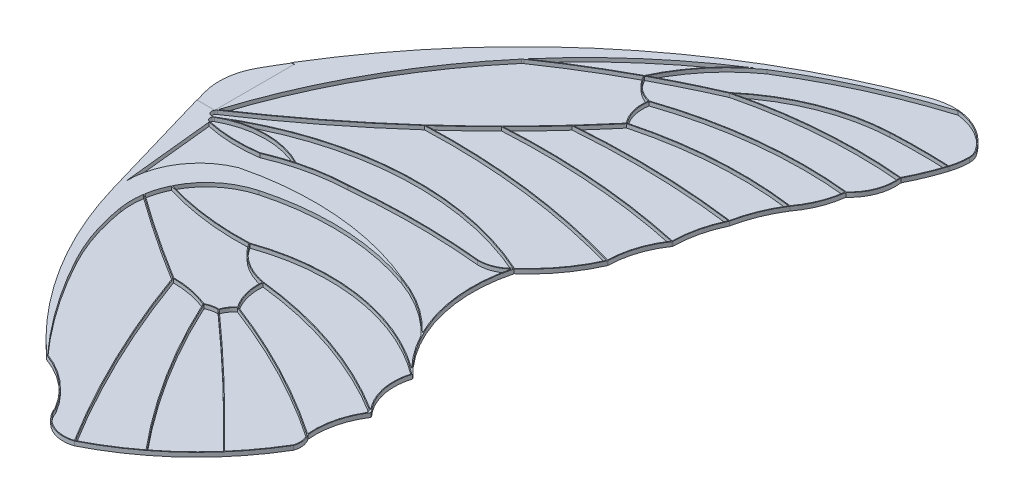
SolidWorks part; units mm, degrees
ref_plane "Plano frontal" through (0, 0, 0) normal (0, 0, 1) x (1, 0, 0)
ref_plane "Plano superior" through (0, 0, 0) normal (0, 1, 0) x (1, 0, 0)
ref_plane "Plano direito" through (0, 0, 0) normal (1, 0, 0) x (0, 0, -1)
sketch "Esboço1" plane through (0, 0, 0) normal (0, 1, 0) x (1, 0, 0)
  line L0 (245.8971, 320.852) -> (1229.6128, 320.852) construction
  line L1 (16.8906, -92.872) -> (-2.8919, -25.3314)
  line L3 (11.8593, -37.4647) -> (16.8906, -86.1328)
  arc A0 (-2.8919, -25.3314) -> (0, 0) centre (28.6286, -16.0991) cw
  arc A1 (0, 0) -> (189.3972, 162.1056) centre (316.3195, -177.8795) cw
  arc A3 (225.6385, 150.4697) -> (227.1081, 145.6019) centre (218.3116, 145.6019) cw construction
  arc A4 (227.1081, 145.6019) -> (225.6385, 136.1666) centre (196.0862, 145.6019) cw construction
  arc A5 (225.6385, 136.1666) -> (218.3116, 118.3563) centre (112.5985, 172.257) cw construction
  arc A7 (218.3116, 118.3563) -> (210.4763, 97.5461) centre (194.6459, 115.3865) cw construction
  arc A8 (210.4763, 97.5461) -> (202.0473, 76.5423) centre (166.9708, 102.8121) cw construction
  arc A9 (202.0473, 76.5423) -> (192.9964, 53.9892) centre (259.2241, 40.5039) ccw construction
  arc A10 (192.9964, 53.9892) -> (187.293, 29.7021) centre (245.6081, 28.8209) ccw construction
  arc A11 (187.293, 29.7021) -> (179.0373, 4.0907) centre (225.0788, 3.3859) ccw construction
  arc A12 (179.0373, 4.0907) -> (158.23, -24.0759) centre (104.6802, 37.2514) cw construction
  arc A15 (158.23, -24.0759) -> (13.4854, -32.4272) centre (93.7944, -165.8093) ccw construction
  arc A16 (158.23, -24.0759) -> (177.8517, -97.0522) centre (231.9136, -43.3901) ccw construction
  arc A17 (8.5132, -29.7405) -> (121.9031, 71.3535) centre (-285.6091, 414.2929) ccw construction
  arc A18 (11.0704, -33.894) -> (11.8796, -37.06) centre (11.8906, -35.3708) ccw
  arc A19 (69.7615, 17.5747) -> (179.0373, 4.0907) centre (83.0084, -324.6055) cw construction
  arc A20 (187.293, 29.7021) -> (90.5728, 37.2507) centre (111.635, -316.2908) ccw construction
  arc A21 (192.9964, 53.9892) -> (108.6142, 56.1566) centre (140.5341, -344.8129) ccw construction
  arc A22 (202.0473, 76.5423) -> (121.9031, 71.3535) centre (174.9731, -126.811) ccw construction
  arc A23 (121.9031, 71.3535) -> (117.6553, 87.2147) centre (137.0585, 83.9116) cw construction
  arc A24 (117.6553, 87.2147) -> (210.4763, 97.5461) centre (187.5432, -118.5488) cw construction
  arc A25 (202.7141, 163.713) -> (134.2312, 132.489) centre (289.7224, -117.8339) ccw
  arc A26 (65.7605, 73.6867) -> (134.9405, 112.1301) centre (303.5466, -272.7489) cw construction
  arc A27 (117.6553, 87.2147) -> (104.9295, 97.5363) centre (122.326, 105.9791) cw construction
  arc A28 (105.0708, 97.8389) -> (131.9285, 131.0439) centre (185.93, 59.9007) cw construction
  arc A29 (134.9405, 112.1301) -> (195.1764, 136.1273) centre (199.9365, 36.5807) cw construction
  arc A30 (134.9405, 112.1301) -> (218.3116, 118.3563) centre (194.9004, -129.4588) cw construction
  arc A31 (195.1764, 136.1273) -> (225.6385, 136.1666) centre (210.8302, -191.2388) cw construction
  arc A32 (164.2786, -78.4304) -> (163.8648, -78.0625) centre (76.6095, -176.6501) ccw construction
  arc A33 (40.2619, -50.4484) -> (16.8906, -86.1328) centre (54.6574, -85.3723) ccw
  arc A34 (11.8377, -37.2556) -> (39.3063, -38.1782) centre (28.1448, 38.8778) ccw construction
  arc A35 (39.3063, -38.1782) -> (77.0189, -29.7405) centre (80.4783, -133.7) cw construction
  arc A36 (77.0189, -29.7405) -> (145.0691, -29.7551) centre (110.9705, -372.2463) cw construction
  arc A37 (145.0691, -29.7551) -> (158.23, -24.0759) centre (145.2218, -12.02) ccw construction
  arc A38 (53.1607, -33.3342) -> (13.4854, -32.4272) centre (32.4211, -72.3358) ccw construction
  arc A39 (38.8997, -20.1148) -> (13.4854, -32.4272) centre (28.6163, -31.2738) cw construction
  arc A40 (16.8906, -92.872) -> (74.9246, -185.6146) centre (210.7556, -36.0892) ccw
  arc A41 (74.9929, -185.4267) -> (66.3816, -175.3804) centre (154.2645, -108.7641) cw construction
  arc A42 (39.4144, -134.6037) -> (75.0612, -185.2387) centre (266.3145, -12.7322) ccw
  arc A43 (74.9929, -185.4267) -> (101.4999, -207.5656) centre (57.6789, -233.0946) cw construction
  arc A44 (101.4999, -207.5656) -> (121.3412, -217.2503) centre (116.2629, -202.4873) ccw construction
  arc A45 (121.3412, -217.2503) -> (180.55, -161.9238) centre (55.9487, -87.924) ccw construction
  arc A46 (180.55, -161.9238) -> (179.3854, -153.5104) centre (171.7806, -158.8504) ccw construction
  arc A47 (179.3754, -98.5448) -> (185.959, -126.7273) centre (206.845, -106.9879) ccw construction
  arc A48 (185.959, -126.7273) -> (179.3854, -153.5104) centre (220.4313, -149.3865) ccw construction
  arc A49 (103.607, -114.0548) -> (179.3854, -153.5104) centre (-25.2756, -454.0845) cw construction
  arc A50 (55.95, -55.4784) -> (133.7088, -58.3585) centre (90.2455, -180.677) cw
  arc A51 (55.95, -55.4784) -> (31.1326, -75.9422) centre (66.32, -93.3351) ccw
  arc A52 (27.5649, -99.5565) -> (39.4144, -134.6037) centre (137.5319, -81.9033) ccw
  arc A53 (27.565, -87.1132) -> (73.2426, -117.5725) centre (461.4317, 514.0462) ccw construction
  arc A54 (73.2426, -117.5725) -> (92.998, -121.4212) centre (73.3114, -169.8452) cw construction
  arc A55 (92.998, -121.4212) -> (99.4217, -119.9985) centre (98.6915, -131.9152) cw construction
  arc A56 (99.4217, -119.9985) -> (103.607, -114.0548) centre (110.0937, -123.0679) cw construction
  arc A57 (103.607, -114.0548) -> (98.6915, -96.0121) centre (125.3192, -98.4486) cw construction
  arc A58 (98.6915, -96.0121) -> (77.4929, -81.9059) centre (103.8031, -65.3487) cw construction
  arc A59 (77.4929, -81.9059) -> (178.9645, -98.1504) centre (113.3271, -183.1111) cw construction
  arc A60 (77.4929, -81.9059) -> (31.0432, -76.1242) centre (71.4634, 59.1311) cw construction
  arc A61 (98.6915, -96.0121) -> (185.959, -126.7273) centre (76.8879, -297.2892) cw construction
  arc A62 (99.4217, -119.9985) -> (165.2455, -183.0853) centre (-749.6332, -1071.7733) cw construction
  arc A63 (92.998, -121.4212) -> (144.3602, -202.7494) centre (428.3218, 33.4673) ccw construction
  arc A64 (73.2426, -117.5725) -> (121.3412, -217.2503) centre (570.6991, 61.0271) ccw construction
  arc A65 (8.6464, -29.8922) -> (10.8842, -33.7922) centre (9.8905, -31.7703) ccw
  arc A66 (65.8737, 73.5218) -> (65.1633, 72.9862) centre (71.5226, 65.2919) ccw
  arc A67 (104.7763, 97.681) -> (130.1059, 129.8789) centre (185.93, 59.9007) cw
  arc A68 (104.7481, 97.6206) -> (150.4255, 142.0756) centre (185.93, 59.9007) cw construction
  arc A69 (104.9295, 97.5363) -> (150.5048, 141.892) centre (185.93, 59.9007) cw construction
  arc A70 (130.1059, 129.8789) -> (66.2643, 74.2743) centre (289.7224, -117.8339) ccw
  arc A71 (65.1633, 72.9862) -> (8.6083, -29.4376) centre (289.7224, -117.8339) ccw
  arc A72 (135.7135, 112.5265) -> (195.186, 135.9275) centre (199.9365, 36.5807) cw
  arc A73 (134.8328, 112.3013) -> (195.1668, 136.3271) centre (199.9365, 36.5807) cw
  arc A74 (65.8737, 73.5218) -> (104.8415, 97.2621) centre (303.5466, -272.7489) cw
  arc A75 (66.2643, 74.2743) -> (104.7763, 97.681) centre (303.5466, -272.7489) cw
  arc A76 (105.3664, 97.9971) -> (134.2312, 132.489) centre (185.93, 59.9007) cw
  arc A77 (105.3664, 97.9971) -> (134.8328, 112.3013) centre (303.5466, -272.7489) cw
  arc A78 (65.6474, 73.8516) -> (134.8603, 112.3133) centre (303.5466, -272.7489) cw construction
  arc A79 (203.4113, 163.9275) -> (225.6385, 150.4697) centre (200.23, 133.5888) cw construction
  arc A80 (203.3904, 163.7286) -> (225.4719, 150.359) centre (200.23, 133.5888) cw
  arc A81 (203.4321, 164.1264) -> (225.805, 150.5804) centre (200.23, 133.5888) cw
  arc A82 (189.3972, 162.1056) -> (203.4321, 164.1264) centre (201.0573, 130.8716) cw
  arc A83 (203.3904, 163.7286) -> (202.7141, 163.713) centre (203.1131, 161.0838) ccw
  arc A84 (225.4719, 150.359) -> (226.9081, 145.6019) centre (218.3116, 145.6019) cw
  arc A85 (226.9081, 145.6019) -> (225.4941, 136.3733) centre (196.0862, 145.6019) cw
  arc A86 (225.805, 150.5804) -> (227.3081, 145.6019) centre (218.3116, 145.6019) cw
  arc A87 (227.3081, 145.6019) -> (225.829, 136.1058) centre (196.0862, 145.6019) cw
  arc A88 (195.186, 135.9275) -> (225.3682, 135.9786) centre (210.8302, -191.2388) cw
  arc A89 (195.1668, 136.3271) -> (225.4941, 136.3733) centre (210.8302, -191.2388) cw
  arc A90 (195.1668, 136.3271) -> (225.6475, 136.3664) centre (210.8302, -191.2388) cw construction
  arc A91 (226.9081, 145.6019) -> (225.4479, 136.2275) centre (196.0862, 145.6019) cw construction
  arc A92 (225.3682, 135.9786) -> (218.195, 118.5681) centre (112.5985, 172.257) cw
  arc A93 (135.0052, 111.9401) -> (218.1326, 118.1722) centre (194.9004, -129.4588) cw
  arc A94 (218.1326, 118.1722) -> (210.4094, 97.7543) centre (194.6459, 115.3865) cw
  arc A95 (225.829, 136.1058) -> (218.5176, 118.3201) centre (112.5985, 172.257) cw
  arc A96 (135.7135, 112.5265) -> (218.195, 118.5681) centre (194.9004, -129.4588) cw
  arc A97 (218.5176, 118.3201) -> (210.6657, 97.4469) centre (194.6459, 115.3865) cw
  arc A98 (225.4479, 136.2275) -> (218.1334, 118.4471) centre (112.5985, 172.257) cw construction
  arc A99 (134.8923, 112.3242) -> (218.3304, 118.5554) centre (194.9004, -129.4588) cw construction
  arc A100 (195.186, 135.9275) -> (225.6294, 135.9669) centre (210.8302, -191.2388) cw construction
  arc A101 (134.8101, 112.2817) -> (195.1668, 136.3271) centre (199.9365, 36.5807) cw construction
  arc A102 (135.0709, 111.9785) -> (195.186, 135.9275) centre (199.9365, 36.5807) cw construction
  arc A103 (134.9887, 111.936) -> (218.2928, 118.1572) centre (194.9004, -129.4588) cw construction
  arc A104 (65.8737, 73.5218) -> (135.0208, 111.9469) centre (303.5466, -272.7489) cw construction
  arc A105 (218.51, 118.3812) -> (210.6091, 97.3965) centre (194.6459, 115.3865) cw construction
  arc A106 (225.829, 136.1058) -> (218.4898, 118.2654) centre (112.5985, 172.257) cw construction
  arc A107 (218.1131, 118.3314) -> (210.3436, 97.6957) centre (194.6459, 115.3865) cw construction
  arc A108 (117.6468, 87.423) -> (105.1942, 97.4512) centre (122.326, 105.9791) cw
  arc A109 (121.9757, 71.58) -> (117.8329, 87.0637) centre (137.0585, 83.9116) cw
  arc A110 (117.8329, 87.0637) -> (210.2529, 97.3685) centre (187.5432, -118.5488) cw
  arc A111 (210.2529, 97.3685) -> (201.9573, 76.7561) centre (166.9708, 102.8121) cw
  arc A112 (117.428, 87.066) -> (104.8415, 97.2621) centre (122.326, 105.9791) cw
  arc A113 (121.643, 71.3551) -> (117.428, 87.066) centre (137.0585, 83.9116) cw
  arc A114 (117.6468, 87.423) -> (210.4094, 97.7543) centre (187.5432, -118.5488) cw
  arc A115 (210.6657, 97.4469) -> (202.2122, 76.4289) centre (166.9708, 102.8121) cw
  arc A116 (105.1942, 97.4512) -> (135.0052, 111.9401) centre (303.5466, -272.7489) cw
  arc A117 (117.607, 87.0206) -> (104.7496, 97.449) centre (122.326, 105.9791) cw construction
  arc A118 (117.7036, 87.4087) -> (105.1094, 97.6236) centre (122.326, 105.9791) cw construction
  arc A119 (121.7491, 71.2259) -> (117.4582, 87.2482) centre (137.0585, 83.9116) cw construction
  arc A120 (117.7197, 87.0253) -> (210.2529, 97.3685) centre (187.5432, -118.5488) cw construction
  arc A121 (122.0571, 71.4811) -> (117.8525, 87.1811) centre (137.0585, 83.9116) cw construction
  arc A122 (117.591, 87.404) -> (210.6988, 97.7235) centre (187.5432, -118.5488) cw construction
  arc A123 (201.7125, 76.3849) -> (192.8379, 54.2118) centre (259.2241, 40.5039) ccw
  arc A124 (210.6988, 97.7235) -> (202.2073, 76.4225) centre (166.9708, 102.8121) cw construction
  arc A125 (202.2122, 76.4289) -> (193.1924, 53.9493) centre (259.2241, 40.5039) ccw
  arc A126 (201.9573, 76.7561) -> (121.9757, 71.58) centre (174.9731, -126.811) ccw
  arc A127 (193.1924, 53.9493) -> (193.1768, 53.9029) centre (192.9964, 53.9892) cw
  arc A128 (8.6464, -29.8922) -> (69.8412, 17.3776) centre (-285.6091, 414.2929) ccw
  arc A129 (8.6083, -29.4376) -> (121.643, 71.3551) centre (-285.6091, 414.2929) ccw
  arc A130 (192.8379, 54.2118) -> (109.1013, 56.3957) centre (140.5341, -344.8129) ccw
  arc A131 (202.2165, 76.4357) -> (193.1924, 53.9493) centre (259.2241, 40.5039) ccw construction
  arc A132 (8.4027, -29.5738) -> (121.7501, 71.4823) centre (-285.6091, 414.2929) ccw construction
  arc A133 (202.0737, 76.7406) -> (121.8513, 71.5467) centre (174.9731, -126.811) ccw construction
  arc A134 (187.0972, 29.9495) -> (91.0867, 37.4813) centre (111.635, -316.2908) ccw
  arc A135 (8.6236, -29.9073) -> (122.0561, 71.2247) centre (-285.6091, 414.2929) ccw construction
  arc A136 (193.0225, 54.1875) -> (108.5983, 56.356) centre (140.5341, -344.8129) ccw construction
  arc A137 (69.8412, 17.3776) -> (178.761, 3.963) centre (83.0084, -324.6055) cw
  arc A138 (109.1013, 56.3957) -> (122.0156, 71.1766) centre (-285.6091, 414.2929) ccw
  arc A139 (201.8781, 76.649) -> (192.8004, 54.0291) centre (259.2241, 40.5039) ccw construction
  arc A140 (210.2529, 97.3685) -> (201.8872, 76.6622) centre (166.9708, 102.8121) cw construction
  arc A141 (201.7125, 76.3849) -> (122.0156, 71.1766) centre (174.9731, -126.811) ccw
  arc A142 (193.1768, 53.9029) -> (187.4952, 29.8402) centre (245.6081, 28.8209) ccw
  arc A143 (187.3768, 29.4721) -> (187.4952, 29.8402) centre (186.8279, 29.8519) ccw
  arc A144 (187.0972, 29.9495) -> (90.5609, 37.4504) centre (111.635, -316.2908) ccw construction
  arc A145 (91.0867, 37.4813) -> (108.709, 55.9635) centre (-285.6091, 414.2929) ccw
  arc A146 (187.4898, 29.4542) -> (90.5847, 37.0511) centre (111.635, -316.2908) ccw construction
  arc A147 (192.6977, 53.8267) -> (187.0972, 29.9495) centre (245.6081, 28.8209) ccw
  arc A148 (192.816, 54.0755) -> (187.0972, 29.9495) centre (245.6081, 28.8209) ccw construction
  arc A149 (192.6977, 53.8267) -> (108.709, 55.9635) centre (140.5341, -344.8129) ccw
  arc A150 (187.3768, 29.4721) -> (179.2373, 4.0876) centre (225.0788, 3.3859) ccw
  arc A151 (70.3073, 17.7955) -> (178.8421, 4.356) centre (83.0084, -324.6055) cw
  arc A152 (186.9587, 29.5703) -> (178.8421, 4.356) centre (225.0788, 3.3859) ccw
  arc A153 (69.7538, 17.7745) -> (178.8421, 4.356) centre (83.0084, -324.6055) cw construction
  arc A154 (70.3073, 17.7955) -> (90.6603, 37.0556) centre (-285.6091, 414.2929) ccw
  arc A155 (69.7692, 17.3748) -> (179.2341, 3.8248) centre (83.0084, -324.6055) cw construction
  arc A156 (187.1288, 29.8164) -> (178.8421, 4.356) centre (225.0788, 3.3859) ccw construction
  arc A157 (186.9587, 29.5703) -> (90.6603, 37.0556) centre (111.635, -316.2908) ccw
  arc A158 (187.4571, 29.5878) -> (179.2341, 3.8248) centre (225.0788, 3.3859) ccw construction
  arc A159 (193.1768, 53.9029) -> (187.4898, 29.4542) centre (245.6081, 28.8209) ccw construction
  arc A160 (178.8547, 4.1721) -> (178.8436, 4.1472) centre (104.6802, 37.2514) cw
  arc A161 (158.1953, -23.8405) -> (10.8842, -33.7922) centre (93.7944, -165.8093) ccw
  arc A162 (179.22, 4.0092) -> (158.4079, -24.186) centre (104.6802, 37.2514) cw
  arc A163 (179.22, 4.0092) -> (158.2644, -24.3113) centre (104.6802, 37.2514) cw construction
  arc A165 (158.1953, -23.8405) -> (13.3822, -32.2559) centre (93.7944, -165.8093) ccw construction
  arc A167 (53.1846, -33.1205) -> (16.3441, -30.9777) centre (32.4211, -72.3358) ccw
  arc A168 (11.8593, -37.4647) -> (39.3612, -38.3724) centre (28.1448, 38.8778) ccw
  arc A169 (39.3612, -38.3724) -> (77.0321, -29.9402) centre (80.4783, -133.7) cw
  arc A170 (77.0321, -29.9402) -> (145.0582, -29.9551) centre (110.9705, -372.2463) cw
  arc A171 (145.0582, -29.9551) -> (157.8482, -24.7583) centre (145.2218, -12.02) ccw
  arc A172 (145.0582, -29.9551) -> (158.3767, -24.2119) centre (145.2218, -12.02) ccw construction
  arc A173 (11.8796, -37.06) -> (39.2515, -37.9841) centre (28.1448, 38.8778) ccw
  arc A174 (39.2515, -37.9841) -> (52.6186, -33.2758) centre (80.4783, -133.7) cw
  arc A175 (77.0057, -29.5409) -> (145.0798, -29.5552) centre (110.9705, -372.2463) cw
  arc A176 (145.0798, -29.5552) -> (157.8927, -24.1424) centre (145.2218, -12.02) ccw
  arc A177 (53.2546, -33.1576) -> (13.3997, -32.2465) centre (32.4211, -72.3358) ccw construction
  arc A178 (11.7958, -37.4511) -> (39.3612, -38.3724) centre (28.1448, 38.8778) ccw construction
  arc A179 (158.2644, -24.3113) -> (13.5886, -32.5986) centre (93.7944, -165.8093) ccw construction
  arc A180 (145.0798, -29.5552) -> (158.0833, -23.94) centre (145.2218, -12.02) ccw construction
  arc A182 (52.6186, -33.2758) -> (11.0704, -33.894) centre (32.4211, -72.3358) ccw
  arc A183 (53.1846, -33.1205) -> (77.0057, -29.5409) centre (80.4783, -133.7) cw
  arc A184 (39.2515, -37.9841) -> (77.0057, -29.5409) centre (80.4783, -133.7) cw construction
  arc A185 (157.8927, -24.1424) -> (16.3441, -30.9777) centre (93.7944, -165.8093) ccw
  arc A186 (178.761, 3.963) -> (158.1953, -23.8405) centre (104.6802, 37.2514) cw
  arc A187 (178.8547, 4.1721) -> (158.1953, -23.8405) centre (104.6802, 37.2514) cw construction
  arc A188 (179.22, 4.0092) -> (179.2373, 4.0876) centre (179.0373, 4.0907) ccw
  arc A189 (157.8482, -24.7583) -> (163.5415, -77.4206) centre (231.9136, -43.3901) ccw
  arc A190 (158.4079, -24.186) -> (179.5133, -98.4) centre (231.9136, -43.3901) ccw
  arc A191 (158.0365, -24.0252) -> (179.2374, -98.6896) centre (231.9136, -43.3901) ccw construction
  arc A192 (133.8427, -57.9816) -> (40.2619, -50.4484) centre (75.882, -192.9794) ccw
  arc A193 (158.4235, -24.1266) -> (179.5133, -98.4) centre (231.9136, -43.3901) ccw construction
  arc A194 (133.7758, -58.17) -> (163.8648, -78.0625) centre (108.6533, -128.872) cw construction
  arc A195 (133.7088, -58.3585) -> (163.7246, -78.2055) centre (108.6533, -128.872) cw
  arc A196 (163.7246, -78.2055) -> (164.2392, -78.7877) centre (149.3526, -91.428) cw
  arc A197 (133.8427, -57.9816) -> (163.5415, -77.4206) centre (108.6533, -128.872) cw
  arc A198 (77.3856, -82.1106) -> (30.9549, -76.3065) centre (71.4634, 59.1311) cw
  arc A199 (133.8427, -57.9816) -> (164.005, -77.9196) centre (108.6533, -128.872) cw construction
  arc A200 (164.1455, -78.5796) -> (163.7246, -78.2055) centre (76.6095, -176.6501) ccw construction
  arc A201 (164.2392, -78.7877) -> (176.8413, -96.3038) centre (231.9136, -43.3901) ccw
  arc A202 (164.4118, -78.2811) -> (164.005, -77.9196) centre (76.6095, -176.6501) ccw construction
  arc A203 (77.7964, -82.0109) -> (178.8422, -98.3087) centre (113.3271, -183.1111) cw
  arc A204 (77.4544, -81.7073) -> (31.1326, -75.9422) centre (71.4634, 59.1311) cw
  arc A205 (77.4544, -81.7073) -> (176.8413, -96.3038) centre (113.3271, -183.1111) cw
  arc A206 (77.5314, -82.1044) -> (30.986, -76.3158) centre (71.4634, 59.1311) cw construction
  arc A207 (30.9549, -76.3065) -> (27.6041, -86.8743) centre (66.32, -93.3351) ccw
  arc A208 (77.4544, -81.7073) -> (31.1005, -75.9326) centre (71.4634, 59.1311) cw construction
  arc A209 (158.23, -24.0759) -> (179.3754, -98.5448) centre (231.9136, -43.3901) ccw construction
  arc A210 (98.7187, -95.8139) -> (77.7964, -82.0109) centre (103.8031, -65.3487) cw
  arc A211 (103.7344, -113.8892) -> (98.8729, -96.233) centre (125.3192, -98.4486) cw
  arc A212 (98.713, -95.8133) -> (184.8389, -125.7798) centre (76.8879, -297.2892) cw construction
  arc A213 (179.5665, -98.6035) -> (185.9696, -126.4464) centre (206.845, -106.9879) ccw
  arc A214 (98.4761, -96.1784) -> (77.3856, -82.1106) centre (103.8031, -65.3487) cw
  arc A215 (103.3296, -114.0103) -> (98.4761, -96.1784) centre (125.3192, -98.4486) cw
  arc A216 (98.7187, -95.8139) -> (184.8389, -125.7798) centre (76.8879, -297.2892) cw
  arc A217 (179.5133, -98.4) -> (179.5665, -98.6035) centre (179.3754, -98.5448) cw
  arc A218 (98.6586, -96.2094) -> (77.3236, -82.0124) centre (103.8031, -65.3487) cw construction
  arc A219 (77.5314, -82.1044) -> (178.8422, -98.3087) centre (113.3271, -183.1111) cw construction
  arc A220 (178.8422, -98.3087) -> (179.0485, -98.9406) centre (178.4809, -98.7763) cw
  arc A221 (98.7244, -95.8148) -> (77.6621, -81.7994) centre (103.8031, -65.3487) cw construction
  arc A222 (77.4544, -81.7073) -> (179.0867, -97.9922) centre (113.3271, -183.1111) cw construction
  arc A223 (99.6493, -119.9335) -> (103.6372, -114.2802) centre (110.0937, -123.0679) cw
  arc A224 (179.0485, -98.9406) -> (184.8389, -125.7798) centre (206.845, -106.9879) ccw
  arc A225 (179.1842, -98.486) -> (184.8389, -125.7798) centre (206.845, -106.9879) ccw construction
  arc A226 (103.6372, -114.2802) -> (179.2425, -153.6551) centre (-25.2756, -454.0845) cw
  arc A227 (186.018, -127.0026) -> (179.5792, -153.4387) centre (220.4313, -149.3865) ccw
  arc A228 (99.2747, -119.7902) -> (103.3296, -114.0103) centre (110.0937, -123.0679) cw
  arc A229 (103.7344, -113.8892) -> (179.1459, -153.1057) centre (-25.2756, -454.0845) cw
  arc A230 (185.7919, -126.6175) -> (185.7905, -126.6196) centre (220.4313, -149.3865) ccw
  arc A231 (184.6648, -128.4325) -> (179.1459, -153.1057) centre (220.4313, -149.3865) ccw
  arc A232 (185.7919, -126.6175) -> (179.1459, -153.1057) centre (220.4313, -149.3865) ccw construction
  arc A233 (186.1262, -126.8372) -> (179.6297, -153.919) centre (220.4313, -149.3865) ccw construction
  arc A234 (98.6699, -96.2109) -> (187.474, -127.9445) centre (76.8879, -297.2892) cw construction
  arc A235 (186.018, -127.0026) -> (185.9696, -126.4464) centre (185.6381, -126.7554) ccw
  arc A236 (179.5665, -98.6035) -> (187.474, -127.9445) centre (206.845, -106.9879) ccw construction
  arc A237 (184.6648, -128.4325) -> (183.9983, -125.7249) centre (182.9391, -127.4215) ccw
  arc A238 (93.2588, -121.5089) -> (99.3405, -120.1941) centre (98.6915, -131.9152) cw
  arc A239 (99.3405, -120.1941) -> (164.9738, -183.0926) centre (-749.6332, -1071.7733) cw
  arc A240 (121.4315, -217.4287) -> (180.7321, -162.0089) centre (55.9487, -87.924) ccw
  arc A241 (180.7321, -162.0089) -> (179.5792, -153.4387) centre (171.7806, -158.8504) ccw
  arc A242 (92.986, -121.2005) -> (99.2747, -119.7902) centre (98.6915, -131.9152) cw
  arc A243 (99.6493, -119.9335) -> (165.2373, -182.7899) centre (-749.6332, -1071.7733) cw
  arc A244 (121.4146, -216.9889) -> (144.0736, -202.7175) centre (55.9487, -87.924) ccw
  arc A245 (180.3678, -161.8389) -> (179.2425, -153.6551) centre (171.7806, -158.8504) ccw
  arc A246 (99.2295, -119.9432) -> (103.578, -113.83) centre (110.0937, -123.0679) cw construction
  arc A247 (103.578, -113.83) -> (179.1459, -153.1057) centre (-25.2756, -454.0845) cw construction
  arc A248 (92.9026, -121.2454) -> (99.5034, -119.8034) centre (98.6915, -131.9152) cw construction
  arc A249 (99.6139, -120.0538) -> (103.6372, -114.2802) centre (110.0937, -123.0679) cw construction
  arc A250 (99.5034, -119.8034) -> (165.389, -182.9459) centre (-749.6332, -1071.7733) cw construction
  arc A251 (103.7694, -113.9381) -> (98.8906, -96.0303) centre (125.3192, -98.4486) cw construction
  arc A252 (103.4446, -114.1716) -> (98.4923, -95.9939) centre (125.3192, -98.4486) cw construction
  arc A253 (180.3678, -161.8389) -> (179.2217, -153.6253) centre (171.7806, -158.8504) ccw construction
  arc A254 (98.8729, -96.233) -> (183.9983, -125.7249) centre (76.8879, -297.2892) cw
  arc A255 (103.6372, -114.2802) -> (179.6297, -153.919) centre (-25.2756, -454.0845) cw construction
  arc A256 (180.7321, -162.0089) -> (179.549, -153.3955) centre (171.7806, -158.8504) ccw construction
  arc A257 (165.3772, -182.9338) -> (165.389, -182.9459) centre (-749.6332, -1071.7733) cw
  arc A258 (165.2373, -182.7899) -> (180.3678, -161.8389) centre (55.9487, -87.924) ccw
  arc A259 (121.251, -217.0718) -> (180.3678, -161.8389) centre (55.9487, -87.924) ccw construction
  arc A260 (99.3405, -120.1941) -> (165.102, -183.2246) centre (-749.6332, -1071.7733) cw construction
  arc A261 (121.4315, -217.4287) -> (121.4146, -217.4365) centre (121.315, -217.1984) cw
  arc A262 (92.8496, -121.5768) -> (144.0736, -202.7175) centre (428.3218, 33.4673) ccw
  arc A263 (73.2991, -117.3724) -> (92.986, -121.2005) centre (73.3114, -169.8452) cw
  arc A264 (93.2588, -121.5089) -> (144.3907, -202.4733) centre (428.3218, 33.4673) ccw
  arc A265 (73.2423, -117.3725) -> (93.1465, -121.2657) centre (73.3114, -169.8452) cw construction
  arc A266 (93.1465, -121.2657) -> (144.5139, -202.6215) centre (428.3218, 33.4673) ccw construction
  arc A267 (93.0933, -121.597) -> (99.3405, -120.1941) centre (98.6915, -131.9152) cw construction
  arc A268 (144.3907, -202.4733) -> (164.9738, -183.0926) centre (55.9487, -87.924) ccw
  arc A269 (74.9246, -185.6146) -> (101.3172, -207.6494) centre (57.6789, -233.0946) cw
  arc A270 (92.8496, -121.5768) -> (144.2064, -202.8773) centre (428.3218, 33.4673) ccw construction
  arc A271 (101.3172, -207.6494) -> (121.4146, -217.4365) centre (116.2629, -202.4873) ccw
  arc A272 (73.5271, -117.7729) -> (121.4146, -216.9889) centre (570.6991, 61.0271) ccw
  arc A273 (27.682, -86.951) -> (73.2991, -117.3724) centre (461.4317, 514.0462) ccw
  arc A274 (75.0612, -185.2387) -> (101.6826, -207.482) centre (57.6789, -233.0946) cw
  arc A275 (101.6826, -207.482) -> (121.0383, -217.1408) centre (116.2629, -202.4873) ccw
  arc A276 (73.0781, -117.7061) -> (121.0383, -217.1408) centre (570.6991, 61.0271) ccw
  arc A277 (27.5301, -87.3346) -> (73.0781, -117.7061) centre (461.4317, 514.0462) ccw
  arc A278 (27.682, -86.951) -> (27.6041, -86.8743) centre (27.8932, -86.6584) cw
  arc A279 (27.5301, -87.3346) -> (27.5649, -99.5565) centre (66.32, -93.3351) ccw
  arc A280 (27.4479, -87.2753) -> (73.0781, -117.7061) centre (461.4317, 514.0462) ccw construction
  arc A281 (27.682, -86.951) -> (73.4071, -117.4388) centre (461.4317, 514.0462) ccw construction
  arc A282 (73.4071, -117.4388) -> (121.6421, -217.3562) centre (570.6991, 61.0271) ccw construction
  arc A283 (73.5271, -117.7729) -> (92.8496, -121.5768) centre (73.3114, -169.8452) cw
  arc A284 (73.2428, -117.7725) -> (92.8496, -121.5768) centre (73.3114, -169.8452) cw construction
  arc A285 (101.3172, -207.6494) -> (121.6421, -217.3562) centre (116.2629, -202.4873) ccw construction
  dimension "D2" = 0.2
  dimension "D3" = 0.2
  dimension "D4" = 0.2
  dimension "D5" = 0.2
  dimension "D41" = 2
  dimension "D1" = 230
  dimension "D6" = 0.2
  dimension "D7" = 0.2
  dimension "D8" = 0.2
  dimension "D9" = 0.2
  dimension "D10" = 0.2
  dimension "D11" = 0.2
  dimension "D12" = 0.2
  dimension "D13" = 0.2
  dimension "D14" = 0.2
  dimension "D15" = 0.2
  dimension "D16" = 0.2
  dimension "D17" = 0.2
  dimension "D18" = 0.2
  dimension "D19" = 0.2
  dimension "D20" = 0.2
  dimension "D21" = 0.2
  dimension "D22" = 0.2
  dimension "D23" = 0.2
  dimension "D24" = 0.2
  dimension "D25" = 0.2
  dimension "D26" = 0.2
  dimension "D27" = 0.2
  dimension "D28" = 0.2
  dimension "D29" = 0.2
  dimension "D30" = 0.2
  dimension "D31" = 0.2
  dimension "D32" = 0.2
  dimension "D33" = 0.2
  dimension "D34" = 0.2
  dimension "D35" = 0.2
  dimension "D36" = 0.2
  dimension "D37" = 0.2
  dimension "D38" = 0.2
  dimension "D39" = 0.2
  dimension "D40" = 0.2
  dimension "D42" = 0.2
  dimension "D43" = 0.2
  dimension "D44" = 0.2
  dimension "D45" = 0.2
  dimension "D46" = 0.2
  dimension "D47" = 0.2
extrude "Ressalto-extrusão1" add sketch "Esboço1" along normal blind 2 contours A269 A271 A261 A240 A241 A227 A235 A213 A217 A190 A162 A188 A150 A143 A142 A127 A125 A115 A97 A95 A87 A86 A81 A82 A1 A0 L1 A40 A279 A277 A276 A275 A274 A42 A52 A211 A254 A237 A231 A229 region at (11.2903, 0, 57.8449)
extrude "Ressalto-extrusão2" add sketch "Esboço1<3>" against normal blind 0.2 contours A186 A137 A128 A65 A161 | A152 A157 A154 A151 | A176 A185 A167 A183 A175 | A192 A197 A189 A171 A170 A169 A168 L3 A33 | A71 A129 A113 A112 A74 A66 | A269 A271 A261 A240 A241 A227 A235 A213 A217 A190 A162 A188 A150 A143 A142 A127 A125 A115 A97 A95 A87 A86 A81 A82 A1 A0 L1 A40 A279 A277 A276 A275 A274 A42 A52 A211 A254 A237 A231 A229 | A174 A182 A18 A173 | A204 A205 A201 A196 A195 A50 A51 | A278 A273 A263 A242 A228 A215 A214 A198 A207 | A224 A220 A203 A210 A216 | A254 A211 A229 A231 A237 | A243 A258 A245 A226 A223 | A264 A268 A239 A238 | A283 A272 A244 A262 | A277 A279 A52 A42 A274 A275 A276 | A147 A149 A145 A134 | A123 A141 A138 A130 | A126 A111 A110 A109 | A116 A108 A114 A94 A93 | A70 A75 A67 | A73 A89 A85 A84 A80 A83 A25 A76 A77 | A72 A96 A92 A88 region at (11.2903, 0, 57.8449) region at (93.3314, 0, 44.0299) region at (30.2552, 0, 33.7407) region at (172.6853, 0, -137.9057) region at (68.277, 0, 149.0902) region at (96.0423, 0, 67.887) region at (105.3792, 0, 1.9385) region at (67.7343, 0, -41.6275) region at (97.2183, 0, -100.0776) region at (187.8294, 0, -126.0632) region at (164.9938, 0, -105.5934) region at (164.8699, 0, -86.5072) region at (159.7192, 0, -66.532) region at (147.0548, 0, -45.7562) region at (134.2713, 0, -24.2683) region at (91.1356, 0, 21.4792) region at (68.1743, 0, 98.0108) region at (134.8048, 0, 93.3656) region at (144.5463, 0, 120.4893) region at (145.9958, 0, 147.7646) region at (130.5494, 0, 164.4613) region at (107.9431, 0, 169.4007)
sketch "Esboço1<3>" plane through (0, 0, 0) normal (0, 1, 0) x (1, 0, 0) same geometry as "Esboço1"
sketch "Esboço2" [suppressed] plane through (0, 2, 0) normal (0, -1, 0) x (1, 0, 0)
  line L1 (6.5158, -11.12) -> (26.2319, -11.12)
  line L2 (6.5158, -11.12) -> (6.5158, -14.12)
  line L3 (6.5158, -14.12) -> (26.2319, -14.12)
  line L4 (26.2319, -11.12) -> (26.2319, -14.12)
  arc A1 (8.6083, 29.4376) -> (65.1633, -72.9862) centre (289.7224, 117.8339) ccw construction
  arc A2 (0, 0) -> (189.3972, -162.1056) centre (316.3195, 177.8795) ccw construction
  point P4 (0, 0)
  point P7 (0, 0)
  point P10 (0, 0)
  point P14 (0, 0)
  point P15 (0, 0)
  dimension "D1" = 11.12
  dimension "D2" = 3
sketch "Esboço3" plane through (0, 2, 0) normal (0, 1, 0) x (1, 0, 0)
  line L1 (-5.5, 11.12) -> (8, 11.12)
  line L2 (-5.5, 11.12) -> (-5.5, -30.63)
  line L3 (-5.5, -30.63) -> (8, -30.63)
  line L4 (8, 11.12) -> (8, -30.63)
  point P4 (0, 0)
  point P5 (0, 0)
  point P6 (0, 0)
  point P9 (0, 0)
  point P10 (0, 0)
  point P14 (0, 0)
  point P17 (0, 0)
  dimension "D1" = 11.12
  dimension "D2" = 30.63
  dimension "D3" = 5.5
  dimension "D4" = 8
extrude "Corte-extrusão2" cut sketch "Esboço3" against normal blind 0.2
